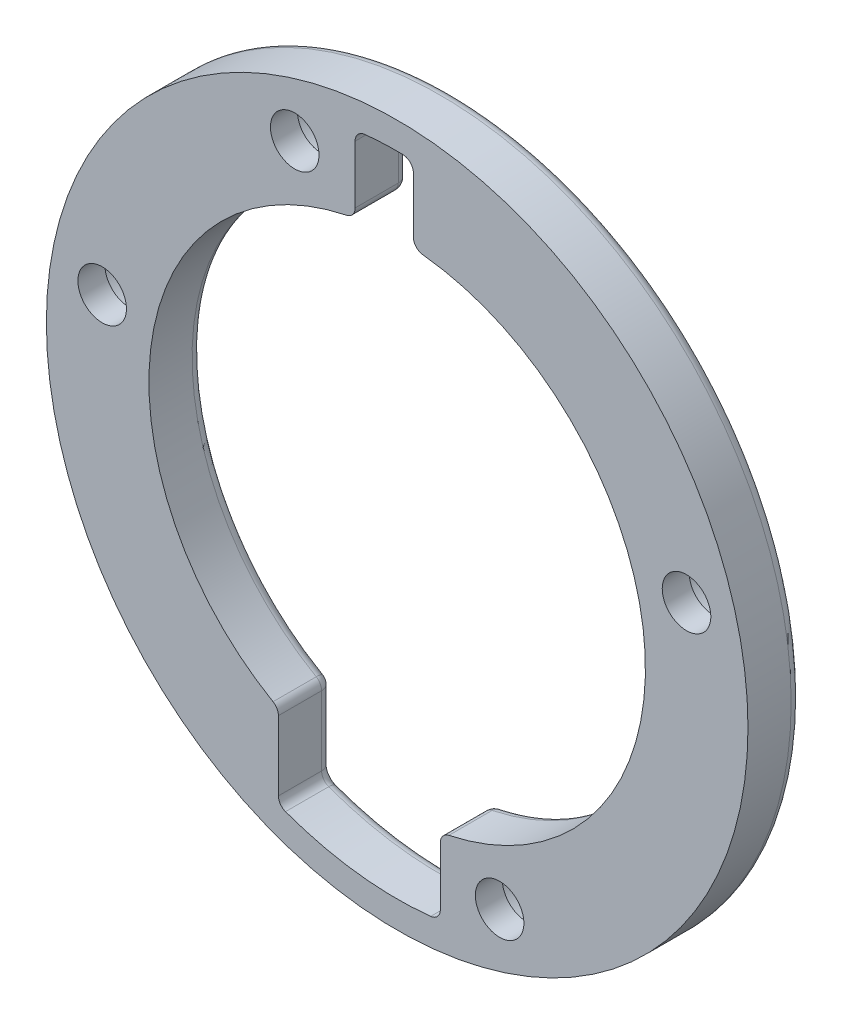
SolidWorks part; units mm, degrees
material "6061-T6 "
ref_plane "Plan de face" through (0, 0, 0) normal (0, 0, 1) x (1, 0, 0)
ref_plane "Plan de dessus" through (0, 0, 0) normal (0, 1, 0) x (1, 0, 0)
ref_plane "Plan de droite" through (0, 0, 0) normal (1, 0, 0) x (0, 0, -1)
sketch "Sketch1" plane through (0, 0, 0) normal (0, 0, 1) x (1, 0, 0)
  line L0 (-9.5, -22) -> (0, -22) construction
  line L1 (0, -22) -> (2.5, -22) construction
  line L3 (-2.5, -28) -> (-4.5, -28) construction
  line L5 (0, 22) -> (0, 27) construction
  line L7 (-9.5, -22) -> (-9.5, -23) construction
  line L9 (2.5, -22) -> (2.5, -23) construction
  line L11 (0, 22) -> (-2.4, 22) construction
  line L12 (-2.4, 22) -> (-2.4, 27) construction
  line L14 (-1.4, 28) -> (-1, 28) construction
  line L18 (4, -22.6495) -> (4, -29.7321)
  line L19 (0, 32.5) -> (0, -32.5) construction
  line L20 (-28.1458, -16.25) -> (28.1458, 16.25) construction
  line L21 (-22.9929, -0.5732) -> (-29.6713, -4.429)
  line L22 (-11, -20.199) -> (-11, -27.9106)
  line L23 (-3.9, 22.6669) -> (-3.9, 29.7454)
  line L24 (1.5, 22.951) -> (1.5, 29.9625)
  line L25 (20.6262, 10.1765) -> (26.6983, 13.6822)
  line L26 (0, 0) -> (26.8044, 7.1822) construction
  line L27 (-27.3284, 4.8187) -> (0, 0) construction
  line L28 (0, 0) -> (9.4911, -26.0765) construction
  line L29 (0, 0) -> (-9.4911, 26.0765) construction
  line L30 (-32.5, 0) -> (32.5, 0) construction
  circle A0 centre (0, 0) radius 28 construction
  circle A1 centre (0, 0) radius 30 construction
  circle A2 centre (0, 0) radius 32.5
  circle A3 centre (0, 0) radius 23
  arc A6 (-9.5, -23) -> (-4.5, -28) centre (-4.5, -23) ccw construction
  arc A7 (2.5, -23) -> (-2.5, -28) centre (-2.5, -23) cw construction
  arc A8 (-2.4, 27) -> (-1.4, 28) centre (-1.4, 27) cw construction
  arc A9 (0, 27) -> (-1, 28) centre (-1, 27) ccw construction
  arc A10 (-29.6713, -4.429) -> (4, -29.7321) centre (0, 0) ccw
  arc A11 (-3.9, 29.7454) -> (26.6983, 13.6822) centre (0, 0) cw
  circle A13 centre (-9.4911, 26.0765) radius 1.65 construction
  circle A14 centre (-27.3284, 4.8187) radius 1.65 construction
  circle A15 centre (9.4911, -26.0765) radius 1.65 construction
  circle A16 centre (26.8044, 7.1822) radius 1.65 construction
  circle A17 centre (0, 0) radius 27.75 construction
  dimension "D1" = 56
  dimension "D9" = 60
  dimension "D10" = 2.5
  dimension "D11" = 46
  dimension "D20" = 10
  dimension "D21" = 15
  dimension "D22" = 20
  dimension "D5" = 5
  dimension "D6" = 1
  dimension "D19" = 3.3
  dimension "D24" = 55.5
  dimension "D2" = 12
  dimension "D3" = 2.5
  dimension "D4" = 6
  dimension "D7" = 2.4
  dimension "D8" = 6
  dimension "D12" = 60
  dimension "D13" = 11
  dimension "D14" = 1.5
  dimension "D15" = 1.5
  dimension "D16" = 1.5
  dimension "D17" = 1.5
  dimension "D18" = 1.5
  dimension "D23" = 20
extrude "Boss-Extrude1" add sketch "Sketch1" against normal blind 5 contours A2 L23 A11 L25 A3 L18 A10 L21 | A11 L24 A3 L25 | L21 A10 L22 A3 region at (-20.6806, -14.8114, 0) region at (13.9466, 21.2914, 0) region at (-31.5808, 0, 0)
sketch "Sketch4" plane through (0, 0, -5) normal (0, 0, -1) x (-1, 0, 0)
  point P0 (27.3284, 4.8187)
  point P3 (9.4911, 26.0765)
  point P6 (-26.8044, 7.1822)
  point P9 (-9.4911, -26.0765)
hole_wizard "CBORE for M4 SHCS1" positions "Sketch4" profile "Sketch3" counterbore size "M4" standard "ANSI Metric" end condition through all
sketch "Sketch3" plane through (-27.3284, 4.8187, -5) normal (1, 0, 0) x (0, 1, 0)
  line L0 (0, 0) -> (0, 5)
  line L1 (0, 5) -> (2.25, 5)
  line L3 (2.25, 5) -> (2.25, 2.5)
  line L4 (2.25, 2.5) -> (4.25, 2.5)
  line L5 (4.25, 2.5) -> (4.25, 0)
  line L7 (4.25, 0) -> (0, 0)
  line L11 (0, -6.35) -> (0, 107.95) construction
  dimension "Thru Hole Dia." = 4.5
  dimension "Thru Hole Depth" = 5
  dimension "C'Bore Dia." = 8.5
  dimension "C'Bore Depth" = 2.5
fillet "Fillet2" radius 1 8 edges at (-11, -20.199, -2.5) (-11, -27.9106, -2.5) (4, -22.6495, -2.5) (4, -29.7321, -2.5) (1.5, 22.951, -2.5) (1.5, 29.9625, -2.5) (-3.9, 22.6669, -2.5) (-3.9, 29.7454, -2.5)
fillet "Fillet3" radius 1 17 edges at (-4.1241, 22.8637, -5) (-3.9, 26.1746, -5) (-3.6416, 29.5255, -5) (-1.2435, 29.9742, -5) (1.2132, 29.6967, -5) (1.5, 26.4326, -5) (1.757, 23.2002, -5) (22.968, 1.2129, -5) (4.2227, -22.8442, -5) (4, -26.1589, -5) (3.7428, -29.5139, -5) (-3.7167, -29.7689, -5) (-10.82, -27.7937, -5) (-11, -24.003, -5) (-11.134, -20.2846, -5) (-22.7099, 3.6415, -5) (32.5, 0, -5)
ref_axis "Axis1" through (9.4911, -26.0765, 0) along (0, 0, -1)
ref_axis "Axis2" through (-9.4911, 26.0765, 0) along (0, 0, -1)
ref_plane "Plane1" through (0, 0, 0) normal (-0.9397, -0.342, 0) x (0, 0, 1)
